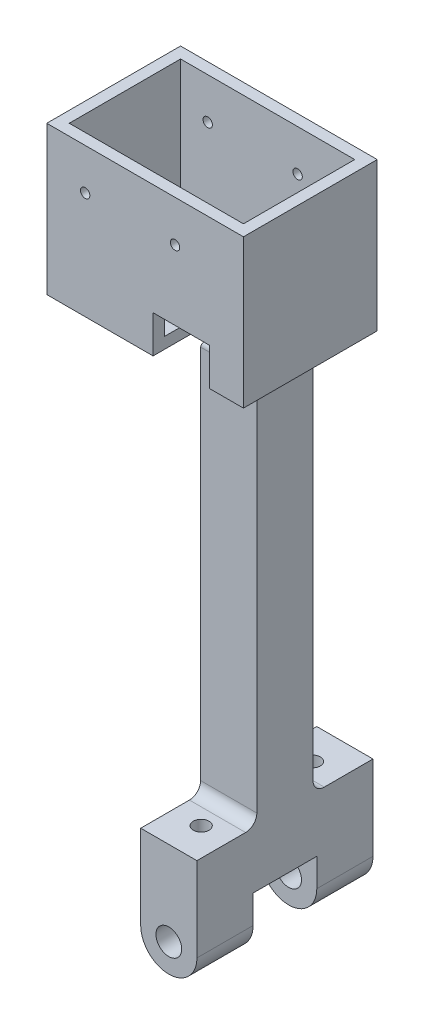
SolidWorks part; units mm, degrees
ref_plane "Plan de face" through (0, 0, 0) normal (0, 0, 1) x (1, 0, 0)
ref_plane "Plan de dessus" through (0, 0, 0) normal (0, 1, 0) x (1, 0, 0)
ref_plane "Plan de droite" through (0, 0, 0) normal (1, 0, 0) x (0, 0, -1)
sketch "Esquisse1" plane through (0, 0, 0) normal (0, 0, 1) x (1, 0, 0)
  line L1 (-15, 64) -> (0, 64)
  line L2 (-15, 64) -> (-15, -64)
  line L4 (0, 64) -> (0, -64)
  arc A0 (-15, -64) -> (0, -64) centre (-7.5, -64) ccw
  point P4 (0, 0)
  point P6 (0, 0)
  point P7 (-7, -63.5)
  point P8 (0, -63.5)
  point P10 (-10, 63.5)
  dimension "D3" = 7.5
  dimension "D1" = 128
  dimension "D2" = 15
extrude "Boss.-Extru.1" add sketch "Esquisse1" along normal blind 47
sketch "Esquisse2" plane through (-15, 0, 0) normal (-1, 0, 0) x (0, 0, 1)
  line L0 (0, -71.5) -> (47, -71.5) construction
  line L1 (15, -71.5) -> (32, -71.5)
  line L2 (15, -71.5) -> (15, -56.5)
  line L3 (15, -56.5) -> (32, -56.5)
  line L4 (32, -71.5) -> (32, -56.5)
  line L5 (0, -8.25) -> (0, 8.25) construction
  line L6 (47, 64) -> (31, 64)
  line L7 (47, 64) -> (47, -41.5)
  line L8 (47, -41.5) -> (31, -41.5)
  line L9 (31, 64) -> (31, -41.5)
  line L10 (0, 64) -> (16, 64)
  line L11 (0, 64) -> (0, -41.5)
  line L12 (0, -41.5) -> (16, -41.5)
  line L13 (16, 64) -> (16, -41.5)
  line L14 (47, 64) -> (0, 64) construction
  line L15 (47, -71.5) -> (47, -64) construction
  point P21 (34.0272, -43.9283)
  point P22 (31.3665, -50.8758)
  point P23 (30.7756, -49.6879)
  point P24 (19.5, -45.459)
  dimension "D2" = 15
  dimension "D1" = 15
  dimension "D3" = 15
  dimension "D4" = 15
  dimension "D5" = 15
extrude "Enlèv. mat.-Extru.1" cut sketch "Esquisse2" against normal through all
sketch "Esquisse3" plane through (-15, 0, 0) normal (-1, 0, 0) x (0, 0, 1)
  line L0 (38.358, 103.2849) -> (38.358, 66.6769)
  line L1 (5.642, 103.2849) -> (8.642, 103.2849)
  line L2 (5.642, 103.2849) -> (5.642, 63.6769)
  line L3 (5.642, 63.6769) -> (41.358, 63.6769)
  line L4 (41.358, 103.2849) -> (41.358, 63.6769)
  line L5 (38.358, 66.6769) -> (8.642, 66.6769)
  line L6 (8.642, 66.6769) -> (8.642, 103.2849)
  line L7 (38.358, 103.2849) -> (41.358, 103.2849)
  line L8 (9.25, 102.8849) -> (9.25, 69.6849) construction
  line L9 (37.75, 102.8849) -> (37.75, 69.6849) construction
  line L11 (13.25, 67.2849) -> (33.75, 67.2849) construction
  line L12 (9.65, 103.2849) -> (11.4157, 103.2849) construction
  point P14 (9.2, 100.3936)
  dimension "D1" = 0.608
  dimension "D2" = 0.608
  dimension "D3" = 0.608
  dimension "D4" = 3
  dimension "D5" = 3
  dimension "D6" = 3
extrude "Boss.-Extru.2" add sketch "Esquisse3" along normal up to vertex (27.72 mm away) and the other way up to vertex (18.78 mm away)
sketch "Esquisse4" plane through (0, 66.6769, 0) normal (0, 1, 0) x (1, 0, 0)
  line L1 (3.78, -5.642) -> (6.78, -5.642)
  line L2 (3.78, -5.642) -> (3.78, -41.358)
  line L3 (3.78, -41.358) -> (6.78, -41.358)
  line L4 (6.78, -5.642) -> (6.78, -41.358)
  line L5 (-42.72, -5.642) -> (-45.72, -5.642)
  line L6 (-42.72, -5.642) -> (-42.72, -41.358)
  line L7 (-42.72, -41.358) -> (-45.72, -41.358)
  line L8 (-45.72, -5.642) -> (-45.72, -41.358)
  point P10 (0, 0)
  point P11 (15.75, -41.358)
  point P13 (-30.75, -41.358)
  dimension "D1" = 3
  dimension "D2" = 3
extrude "Boss.-Extru.5" add sketch "Esquisse4" along normal up to surface and the other way up to surface up to face at (-19.47, 103.2849, 7.142) other way up to face at (-19.47, 63.6769, 23.5)
sketch "Esquisse5" plane through (0, 0, 41.358) normal (0, 0, 1) x (1, 0, 0)
  circle A0 centre (-11.47, 92.2849) radius 1.25
  circle A1 centre (-35.47, 92.2849) radius 1.25
  point P12 (0, 0)
  point P13 (-2.6823, 74.4185)
  dimension "D1" = 2.5
  dimension "D2" = 2.5
extrude "Enlèv. mat.-Extru.2" cut sketch "Esquisse5" along direction (0, 0, -1) on the side against the normal through all
sketch "Esquisse6" plane through (0, 63.6769, 0) normal (0, -1, 0) x (1, 0, 0)
  line L0 (-45.72, 41.358) -> (6.78, 41.358) construction
  line L1 (-17.335, 41.358) -> (-2.335, 41.358)
  line L2 (-17.335, 41.358) -> (-17.335, 29.358)
  line L3 (-17.335, 29.358) -> (-2.335, 29.358)
  line L4 (-2.335, 41.358) -> (-2.335, 29.358)
  line L5 (-45.72, 5.642) -> (6.78, 5.642) construction
  line L6 (-17.335, 5.642) -> (-2.335, 5.642)
  line L7 (-17.335, 5.642) -> (-17.335, 17.642)
  line L8 (-17.335, 17.642) -> (-2.335, 17.642)
  line L9 (-2.335, 5.642) -> (-2.335, 17.642)
  dimension "D2" = 15
  dimension "D1" = 12
  dimension "D3" = 15
  dimension "D4" = 12
extrude "Enlèv. mat.-Extru.3" cut sketch "Esquisse6" against normal blind 10
fillet "Congé1" radius 2 4 edges at (-15, 63.6769, 23.5) (-1.1675, 63.6769, 31) (0, 63.6769, 23.5) (-1.1675, 63.6769, 16)
fillet "Congé2" radius 3 2 edges at (-7.5, -41.5, 16) (-7.5, -41.5, 31)
sketch "Esquisse9" plane through (0, 0, 47) normal (0, 0, 1) x (1, 0, 0)
  circle A0 centre (-7.5, -64) radius 3.429
  point P2 (-7.5, -64)
  dimension "D1" = 6.858
extrude "Enlèv. mat.-Extru.4" cut sketch "Esquisse9" against normal through all
hole_wizard "Trou pour taraudage pour trou taraudé M52" positions "Esquisse15" profile "Esquisse16" hole size "M5" standard "ISO"
sketch "Esquisse15" plane through (0, -41.5, 0) normal (0, 1, 0) x (1, 0, 0)
  line L0 (-42.72, -8.642) -> (3.78, -8.642) construction
  line L1 (-42.72, -38.358) -> (3.78, -38.358) construction
  point P27 (-7.5, -8.642)
  point P31 (-7.5, -38.358)
  point P36 (0, 0)
  point P37 (0, 0)
sketch "Esquisse16" plane through (-7.5, -41.5, 8.642) normal (1, 0, 0) x (0, 0, 1)
  line L0 (0, 0) -> (0, 19.071)
  line L1 (0, 19.071) -> (2.1, 19.071)
  line L2 (2.1, 19.071) -> (2.1, 0)
  line L5 (2.1, 0) -> (0, 0)
  line L11 (0, -6.35) -> (0, 107.95) construction
  dimension "Diamètre du perçage jusqu'au prochain" = 4.2
  dimension "Profondeur du perçage jusqu'au prochain" = 19.071
fillet "Congé3" radius 2 4 edges at (-8.6675, 63.6769, 16) (-15, 63.6769, 16.821) (-8.6675, 63.6769, 31) (-15, 63.6769, 30.179)
equation "\"D3@Esquisse1\"=\"D2@Esquisse1\"/2"
equation "\"7mmmm\"=10"
equation "\"D2@Esquisse2\"=\"D1@Esquisse2\""
equation "\"D3@Esquisse2\"=\"D1@Esquisse2\""
equation "\"D4@Esquisse2\"=\"D1@Esquisse2\""
equation "\"D2@Esquisse3\"=\"D1@Esquisse3\""
equation "\"D4@Esquisse6\"=\"D1@Esquisse6\""
